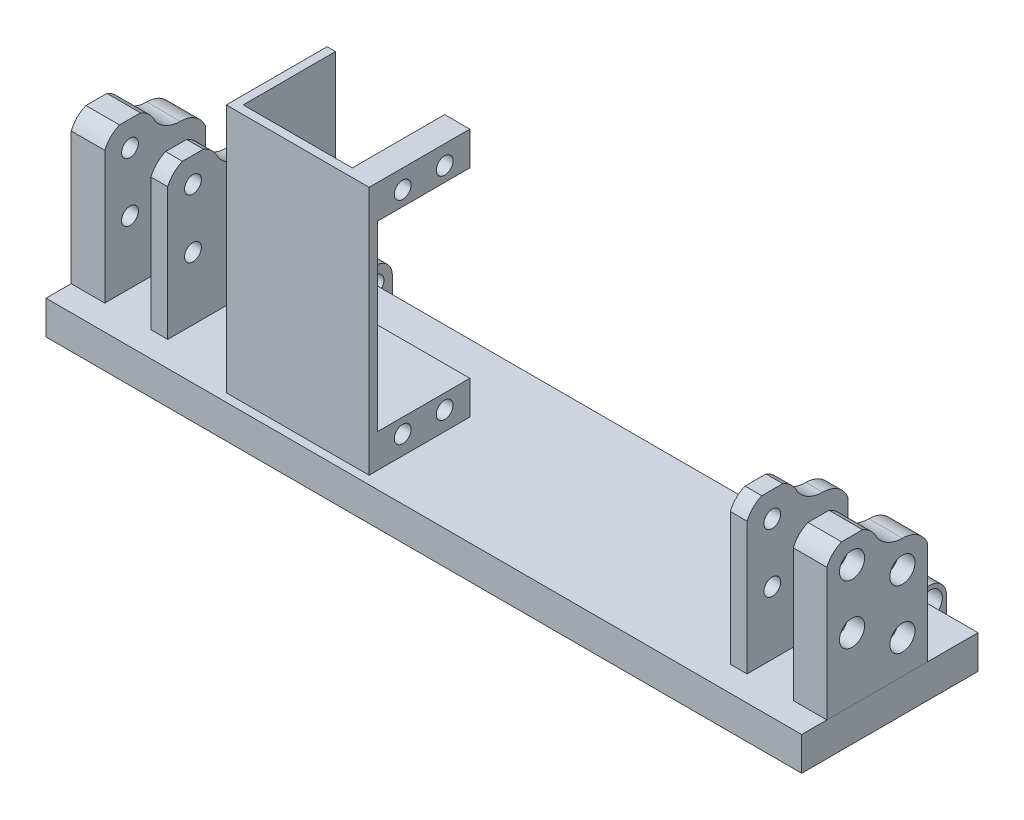
SolidWorks part; units mm, degrees
ref_plane "Plan de face" through (0, 0, 0) normal (0, 0, 1) x (1, 0, 0)
ref_plane "Plan de dessus" through (0, 0, 0) normal (0, 1, 0) x (1, 0, 0)
ref_plane "Plan de droite" through (0, 0, 0) normal (1, 0, 0) x (0, 0, -1)
sketch "Esquisse1" plane through (0, 0, 0) normal (0, 1, 0) x (1, 0, 0)
  line L1 (0, 0) -> (180, 0)
  line L2 (0, 0) -> (0, 42)
  line L3 (0, 42) -> (180, 42)
  line L4 (180, 0) -> (180, 42)
  dimension "D1" = 42
  dimension "D2" = 180
extrude "Boss.-Extru.1" add sketch "Esquisse1" along normal blind 8
sketch "Esquisse3" plane through (0, 8, 0) normal (0, 1, 0) x (1, 0, 0)
  line L1 (41, 1.9615) -> (75, 1.9615)
  line L2 (41, 1.9615) -> (41, 25.9615)
  line L3 (41, 25.9615) -> (75, 25.9615)
  line L4 (75, 1.9615) -> (75, 25.9615)
  line L5 (90, 42) -> (90, 0) construction
  line L6 (180, 42) -> (0, 42) construction
  line L7 (0, 0) -> (180, 0) construction
  dimension "D1" = 34
  dimension "D2" = 24
  dimension "D3" = 49
extrude "Boss.-Extru.2" add sketch "Esquisse3" along normal blind 59.4
sketch "Esquisse4" plane through (0, 67.4, 0) normal (0, 1, 0) x (1, 0, 0)
  line L0 (75, 25.9615) -> (41, 25.9615) construction
  line L1 (43, 25.9615) -> (69, 25.9615)
  line L2 (43, 25.9615) -> (43, 3.9615)
  line L3 (43, 3.9615) -> (69, 3.9615)
  line L4 (69, 25.9615) -> (69, 3.9615)
  line L5 (41, 25.9615) -> (41, 1.9615) construction
  line L6 (41, 1.9615) -> (75, 1.9615) construction
  line L7 (75, 1.9615) -> (75, 25.9615) construction
  point P10 (58, 1.9615)
  dimension "D1" = 2
  dimension "D2" = 2
  dimension "D3" = 6
extrude "Enlèv. mat.-Extru.1" cut sketch "Esquisse4" against normal offset from surface (51.4 mm away) 8 contours L2 L1 L4 L3 up to face at (90, 8, -21)
sketch "Esquisse5" plane through (75, 0, 0) normal (1, 0, 0) x (0, 0, -1)
  line L0 (9.9615, 12.5) -> (19.9615, 12.5) construction
  line L1 (25.9615, 67.4) -> (25.9615, 8) construction
  line L2 (25.9615, 59.4) -> (3.9615, 59.4)
  line L3 (25.9615, 59.4) -> (25.9615, 16)
  line L4 (25.9615, 16) -> (3.9615, 16)
  line L5 (3.9615, 59.4) -> (3.9615, 16)
  line L6 (1.9615, 67.4) -> (25.9615, 67.4) construction
  line L7 (1.9615, 8) -> (25.9615, 8) construction
  line L8 (1.9615, 67.4) -> (1.9615, 8) construction
  line L9 (3.9615, 37.7) -> (25.9615, 37.7) construction
  line L10 (14.9615, 16) -> (14.9615, 12.5) construction
  circle A0 centre (9.9615, 12.5) radius 2
  circle A1 centre (19.9615, 12.5) radius 2
  circle A2 centre (19.9615, 62.9) radius 2
  circle A3 centre (9.9615, 62.9) radius 2
  point P16 (1.9615, 37.7)
  dimension "D4" = 4
  dimension "D1" = 8
  dimension "D2" = 3.5
  dimension "D3" = 8
  dimension "D5" = 2
  dimension "D6" = 10
extrude "Enlèv. mat.-Extru.2" cut sketch "Esquisse5" against normal blind 25
sketch "Esquisse7" plane through (0, 8, 0) normal (0, 1, 0) x (1, 0, 0)
  line L0 (90, 42) -> (90, 29.1788) construction
  line L1 (0, 30) -> (23, 30) construction
  line L2 (0, 30) -> (0, 6)
  line L3 (0, 6) -> (23, 6) construction
  line L4 (23, 30) -> (23, 6)
  line L5 (180, 42) -> (0, 42) construction
  line L6 (19, 30) -> (19, 6)
  line L7 (8, 30) -> (8, 6)
  line L8 (0, 30) -> (8, 30)
  line L9 (19, 30) -> (23, 30)
  line L10 (23, 6) -> (19, 6)
  line L11 (8, 6) -> (0, 6)
  line L12 (180, 6) -> (157, 6) construction
  line L13 (180, 30) -> (157, 30) construction
  line L14 (172, 6) -> (180, 6)
  line L15 (157, 6) -> (161, 6)
  line L16 (161, 30) -> (157, 30)
  line L17 (180, 30) -> (172, 30)
  line L18 (172, 30) -> (172, 6)
  line L19 (161, 30) -> (161, 6)
  line L20 (157, 30) -> (157, 6)
  line L21 (180, 30) -> (180, 6)
  line L22 (0, 42) -> (0, 0) construction
  dimension "D2" = 24
  dimension "D3" = 11
  dimension "D4" = 4
  dimension "D5" = 8
  dimension "D6" = 12
extrude "Boss.-Extru.4" add sketch "Esquisse7" along normal blind 35 separate body
sketch "Esquisse8" plane through (0, 0, 0) normal (-1, 0, 0) x (0, 0, 1)
  line L0 (-24, 30) -> (-24, 16) construction
  line L1 (-12, 37) -> (-12, 23) construction
  line L2 (-24, 30) -> (-12, 30) construction
  line L3 (-30, 43) -> (-30, 8) construction
  line L4 (-30, 43) -> (-6, 43) construction
  line L5 (-6, 43) -> (-6, 8) construction
  line L6 (-9.5, 43) -> (-6, 43)
  line L7 (-6, 43) -> (-6, 39.5)
  line L9 (-30, 32.5) -> (-30, 43)
  line L10 (-30, 43) -> (-14.5, 43)
  line L12 (-24, 36.5) -> (-18, 36.5) construction
  line L13 (-18, 30) -> (-18, 40.6298) construction
  circle A11 centre (-24, 30) radius 2
  circle A12 centre (-12, 37) radius 2
  circle A13 centre (-12, 23) radius 2
  circle A14 centre (-24, 16) radius 2
  circle A15 centre (-12, 37) radius 6.5 construction
  circle A16 centre (-24, 30) radius 6.5 construction
  circle A17 centre (-12, 23) radius 6.5 construction
  circle A18 centre (-24, 16) radius 6.5 construction
  arc A19 (-9.5, 43) -> (-6, 39.5) centre (-12, 37) cw
  arc A20 (-30, 32.5) -> (-24, 36.5) centre (-24, 30) cw
  arc A21 (-14.5, 43) -> (-18, 39.5) centre (-12, 37) ccw
  arc A22 (-18, 39.5) -> (-24, 36.5) centre (-24, 44) cw
  point P8 (-18, 30)
  dimension "D3" = 4
  dimension "D5" = 13
  dimension "D6" = 13
  dimension "D1" = 14
  dimension "D2" = 12
  dimension "D4" = 12
extrude "Enlèv. mat.-Extru.3" cut sketch "Esquisse8" against normal up to surface (23 mm away) contours A11 | A12 | A22 A20 L9 L10 A21 | L7 A19 L6 | A13 | A14 up to face at (23, 25.5, -18)
sketch "Esquisse9" plane through (0, 0, 0) normal (-1, 0, 0) x (0, 0, 1)
  circle A0 centre (-12, 37) radius 3
  circle A1 centre (-24, 30) radius 3
  circle A2 centre (-12, 23) radius 3
  circle A3 centre (-24, 16) radius 3
  dimension "D1" = 6
extrude "Enlèv. mat.-Extru.4" cut sketch "Esquisse9" against normal offset from surface (4 mm away) 4 up to face at (8, 30, -22)
ref_plane "Plan1" through (15.5, 0, 0) normal (-1, 0, 0) x (0, 0, 1)
sketch "Esquisse10" plane through (15.5, 0, 0) normal (-1, 0, 0) x (0, 0, 1)
  line L0 (-46, 8) -> (-42, 8)
  line L1 (-42, 8) -> (-50, 8) construction
  line L2 (-42, 8) -> (-42, 0)
  line L3 (-42, 0) -> (-50, 0)
  line L4 (-50, 8) -> (-50, 0) construction
  line L6 (-50, 4) -> (-50, 0)
  line L7 (-50, 0) -> (-42, 8) construction
  circle A1 centre (-46, 4) radius 2
  arc A2 (-46, 8) -> (-50, 4) centre (-46, 4) ccw
  dimension "D3" = 4
  dimension "D1" = 8
  dimension "D2" = 8
extrude "Boss.-Extru.5" add sketch "Esquisse10" against normal blind 17
sketch "Esquisse11" plane through (15.5, 0, 0) normal (-1, 0, 0) x (0, 0, 1)
  circle A0 centre (-46, 4) radius 3
  dimension "D1" = 6
extrude "Enlèv. mat.-Extru.5" cut sketch "Esquisse11" against normal blind 4
sketch "Esquisse12" plane through (0, 8, 0) normal (0, 1, 0) x (1, 0, 0)
  line L0 (32.5, 50) -> (15.5, 50) construction
  line L1 (23.5, 50) -> (28.5, 50)
  line L2 (23.5, 50) -> (23.5, 41)
  line L3 (23.5, 41) -> (28.5, 41)
  line L4 (28.5, 50) -> (28.5, 41)
  line L5 (32.5, 46) -> (32.5, 50) construction
  dimension "D1" = 9
  dimension "D2" = 5
  dimension "D3" = 4
extrude "Enlèv. mat.-Extru.6" cut sketch "Esquisse12" against normal blind 8
ref_plane "Plan2" through (90, 0, 0) normal (-1, 0, 0) x (0, 0, 1)
mirror "Symétrie9" about plane through (90, 0, 0) normal (-1, 0, 0) of "Enlèv. mat.-Extru.3", "Enlèv. mat.-Extru.4"
ref_plane "Plan3" through (164.5, 0, 0) normal (1, 0, 0) x (0, 0, -1)
sketch "Esquisse13" plane through (164.5, 0, 0) normal (1, 0, 0) x (0, 0, -1)
  line L0 (42, 8) -> (50, 0) construction
  line L1 (42, 0) -> (50, 0)
  line L2 (42, 0) -> (42, 8)
  line L3 (42, 8) -> (50, 8) construction
  line L4 (50, 0) -> (50, 8) construction
  line L5 (42, 8) -> (46, 8)
  line L6 (50, 4) -> (50, 0)
  arc A0 (46, 8) -> (50, 4) centre (46, 4) cw
  circle A1 centre (46, 4) radius 2
  dimension "D3" = 4
  dimension "D1" = 8
  dimension "D2" = 8
extrude "Boss.-Extru.6" add sketch "Esquisse13" against normal blind 17
sketch "Esquisse18" plane through (164.5, 0, 0) normal (1, 0, 0) x (0, 0, -1)
  circle A0 centre (46, 4) radius 3
  dimension "D1" = 6
extrude "Enlèv. mat.-Extru.9" cut sketch "Esquisse18" against normal blind 4
sketch "Esquisse19" plane through (0, 8, 0) normal (0, 1, 0) x (1, 0, 0)
  line L0 (147.5, 50) -> (164.5, 50) construction
  line L1 (151.5, 50) -> (156.5, 50)
  line L2 (151.5, 50) -> (151.5, 41)
  line L3 (151.5, 41) -> (156.5, 41)
  line L4 (156.5, 50) -> (156.5, 41)
  line L5 (147.5, 50) -> (147.5, 46) construction
  dimension "D1" = 5
  dimension "D2" = 4
  dimension "D3" = 9
extrude "Enlèv. mat.-Extru.10" cut sketch "Esquisse19" against normal blind 8
